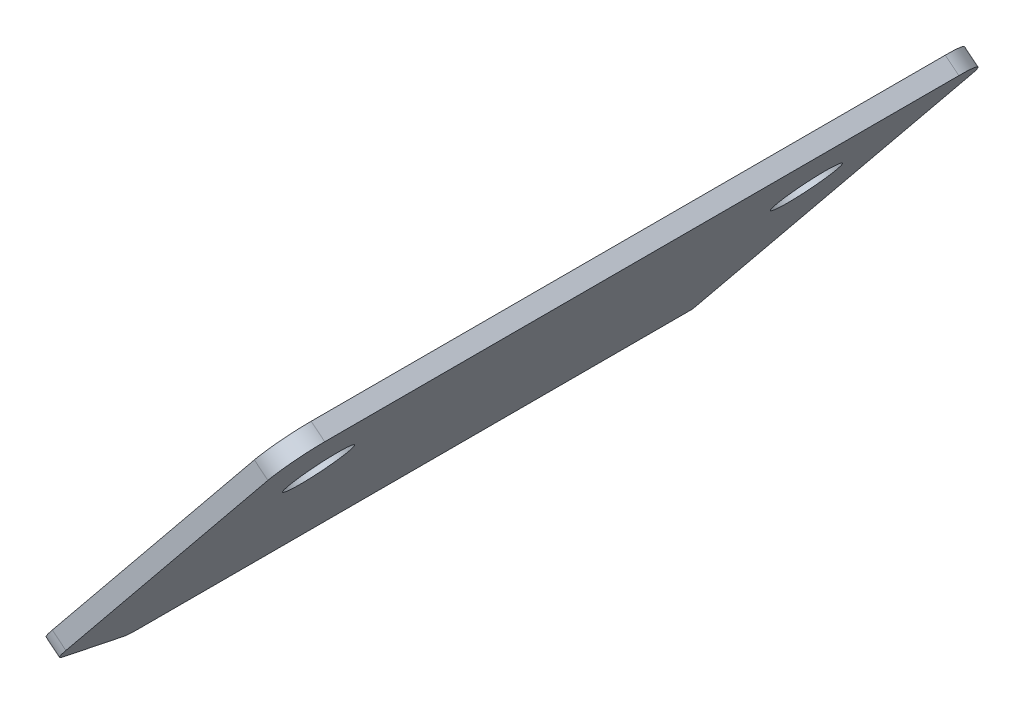
SolidWorks part; units mm, degrees
ref_plane "Front Plane" through (0, 0, 0) normal (0, 0, 1) x (1, 0, 0)
ref_plane "Top Plane" through (0, 0, 0) normal (0, 1, 0) x (1, 0, 0)
ref_plane "Right Plane" through (0, 0, 0) normal (1, 0, 0) x (0, 0, -1)
sketch "Sketch1" plane through (0, 0, 0) normal (0, 0, 1) x (1, 0, 0)
  line L0 (-453.1532, -415.824) -> (-562.8553, -550.6808)
  line L1 (-117.475, -3.175) -> (-517.2676, -494.6397) construction
  line L2 (-562.8553, -550.6808) -> (-567.7813, -546.6736)
  line L3 (-567.7813, -546.6736) -> (-458.0792, -411.8169)
  line L4 (-458.0792, -411.8169) -> (-453.1532, -415.824)
  circle A1 centre (-615.95, -615.95) radius 84.1375 construction
  point P8 (-517.2676, -494.6397)
  dimension "D1" = 6.35
  dimension "D2" = 101.6
extrude "Boss-Extrude1" add sketch "Sketch1" along normal up to surface (256.54 mm away)
sketch "Sketch2" plane through (-74.0659, 60.2505, 0) normal (-0.7757, 0.631, 0) x (0, 0, 1)
  line L0 (128.27, -608.5342) -> (121.92, -710.1342) construction
  line L1 (256.54, -608.5342) -> (0, -608.5342) construction
  line L2 (243.84, -710.1342) -> (0, -710.1342) construction
  line L3 (213.995, -659.3342) -> (36.195, -659.3342) construction
  circle A0 centre (213.995, -659.3342) radius 11.1125
  circle A1 centre (36.195, -659.3342) radius 11.1125
  point P8 (125.095, -659.3342)
  dimension "D2" = 22.225
  dimension "D1" = 177.8
extrude "Cut-Extrude1" cut sketch "Sketch2" against normal up to next
sketch "Sketch3" plane through (-69.1399, 56.2433, 0) normal (0.7757, -0.631, 0) x (0, 0, -1)
  line L0 (-205.74, -782.3757) -> (-256.54, -744.2757)
  line L1 (-256.54, -782.3757) -> (0, -782.3757) construction
  line L2 (-256.54, -782.3757) -> (-256.54, -608.5342) construction
  dimension "D1" = 50.8
  dimension "D2" = 38.1
extrude "Cut-Extrude2" cut sketch "Sketch3" against normal through all and the other way through all
fillet "Fillet1" radius 12.7 4 edges at (-541.2754, -519.1213, 256.54) (-565.3183, -548.6772, 205.74) (-455.6162, -413.8205, 0) (-455.6162, -413.8205, 256.54)
